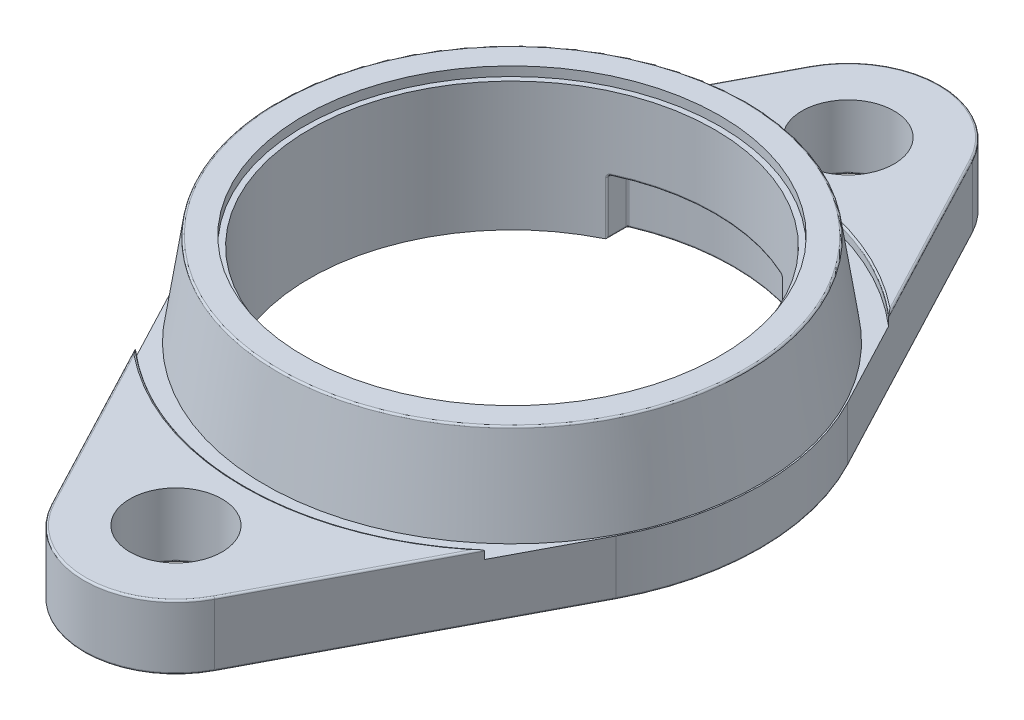
SolidWorks part; units mm, degrees
material "Zinco AC41A Liga, como fundido"
ref_plane "Plano frontal" through (0, 0, 0) normal (0, 0, 1) x (1, 0, 0)
ref_plane "Plano superior" through (0, 0, 0) normal (0, 1, 0) x (1, 0, 0)
ref_plane "Plano direito" through (0, 0, 0) normal (1, 0, 0) x (0, 0, -1)
sketch "Esboço3" plane through (0, 0, 0) normal (0, 1, 0) x (1, 0, 0)
  line L0 (-11.9463, 6.2877) -> (-4.4246, 20.5788)
  line L1 (4.4246, 20.5788) -> (11.9463, 6.2877)
  line L2 (-11.9463, -6.2877) -> (-4.4246, -20.5788)
  line L3 (4.4246, -20.5788) -> (11.9463, -6.2877)
  circle A0 centre (0, 0) radius 11
  arc A1 (-11.9463, 6.2877) -> (-11.9463, -6.2877) centre (0, 0) ccw
  arc A2 (-4.4246, 20.5788) -> (4.4246, 20.5788) centre (0, 18.25) cw
  arc A3 (-4.4246, -20.5788) -> (4.4246, -20.5788) centre (0, -18.25) ccw
  arc A4 (11.9463, -6.2877) -> (11.9463, 6.2877) centre (0, 0) ccw
  circle A5 centre (0, 18.25) radius 2.5
  circle A6 centre (0, -18.25) radius 2.5
  dimension "D1" = 22
  dimension "D2" = 27
  dimension "D4" = 46.5
  dimension "D3" = 5
  dimension "D5" = 5
  dimension "D6" = 5
extrude "Ressalto-extrusão1" add sketch "Esboço3" along normal blind 3
sketch "Esboço4" plane through (0, 0, 0) normal (1, 0, 0) x (0, 0, -1)
  line L0 (0, 0) -> (0, 3) construction
  line L1 (6.2877, 3) -> (-6.2877, 3) construction
  line L2 (-11, 3) -> (-11, 7.5)
  line L3 (-11, 7.5) -> (-11.3, 7.5)
  line L4 (-11.3, 7.5) -> (-11.3, 8)
  line L5 (-11.3, 8) -> (-12.675, 8)
  line L6 (-12.675, 8) -> (-13.425, 3)
  line L7 (-20.5788, 3) -> (-6.2877, 3) construction
  line L8 (-13.425, 3) -> (-11, 3)
  dimension "D1" = 4.5
  dimension "D2" = 12.675
  dimension "D3" = 13.425
  dimension "D4" = 0.5
  dimension "D5" = 0.3
revolve "Revolução1" add sketch "Esboço4" angle 360 about L0
sketch "Esboço6" plane through (0, 3, 0) normal (0, 1, 0) x (1, 0, 0)
  line L0 (-9.4818, 10.9702) -> (-4.4246, 20.5788)
  line L1 (-4.4246, 20.5788) -> (-11.9463, 6.2877) construction
  line L2 (4.4246, 20.5788) -> (9.4818, 10.9702)
  line L3 (11.9463, 6.2877) -> (4.4246, 20.5788) construction
  line L4 (-9.4818, -10.9702) -> (-4.4246, -20.5788)
  line L5 (-11.9463, -6.2877) -> (-4.4246, -20.5788) construction
  line L6 (4.4246, -20.5788) -> (9.4818, -10.9702)
  line L7 (4.4246, -20.5788) -> (11.9463, -6.2877) construction
  arc A0 (-4.4246, 20.5788) -> (4.4246, 20.5788) centre (0, 18.25) cw
  arc A1 (-4.4246, -20.5788) -> (4.4246, -20.5788) centre (0, -18.25) ccw
  arc A2 (-9.4818, -10.9702) -> (9.4818, -10.9702) centre (0, 0) ccw
  arc A3 (9.4818, 10.9702) -> (-9.4818, 10.9702) centre (0, 0) ccw
  dimension "D1" = 29
extrude "Ressalto-extrusão2" add sketch "Esboço6" along normal blind 0.5
sketch "Esboço7" plane through (0, 0, 0) normal (0, -1, 0) x (1, 0, 0)
  line L11 (-2.876, -19.7637) -> (-10.3977, -5.4726)
  line L12 (-10.3977, 5.4726) -> (-2.876, 19.7637)
  line L13 (-4.3256, -17.0094) -> (-10.3977, -5.4726)
  line L14 (-10.3977, 5.4726) -> (-4.3256, 17.0094)
  line L19 (10.3977, -5.4726) -> (2.876, -19.7637)
  line L20 (2.876, 19.7637) -> (10.3977, 5.4726)
  line L21 (10.3977, -5.4726) -> (4.3256, -17.0094)
  line L22 (4.3256, 17.0094) -> (10.3977, 5.4726)
  arc A5 (-10.3977, 5.4726) -> (-10.3977, -5.4726) centre (0, 0) ccw
  arc A6 (-10.3977, 5.4726) -> (-10.3977, -5.4726) centre (0, 0) ccw
  arc A8 (4.3256, -17.0094) -> (-4.3256, -17.0094) centre (0, -18.25) ccw
  arc A9 (10.3977, -5.4726) -> (10.3977, 5.4726) centre (0, 0) ccw
  arc A10 (10.3977, -5.4726) -> (10.3977, 5.4726) centre (0, 0) ccw
  arc A11 (-4.3256, 17.0094) -> (4.3256, 17.0094) centre (0, 18.25) ccw
  dimension "D3" = 9
  dimension "D1" = 1.75
  dimension "D2" = 1.75
extrude "Corte-extrusão1" cut sketch "Esboço7" against normal blind 0.5
sketch "Esboço8" plane through (0, 0.5, 0) normal (0, -1, 0) x (1, 0, 0)
  line L0 (-4.75, 11.0199) -> (-4.75, 9.9216)
  line L1 (4.75, 11.0199) -> (4.75, 9.9216)
  line L2 (0, 0) -> (0, -15.75) construction
  line L3 (-4.75, -9.9216) -> (-4.75, -11.0199)
  line L4 (4.75, -9.9216) -> (4.75, -11.0199)
  arc A0 (-4.75, -11.0199) -> (4.75, -11.0199) centre (0, 0) ccw
  circle A3 centre (0, 0) radius 11 construction
  circle A4 centre (0, -18.25) radius 2.5 construction
  arc A5 (-4.75, -9.9216) -> (4.75, -9.9216) centre (0, 0) ccw
  arc A6 (4.75, 9.9216) -> (-4.75, 9.9216) centre (0, 0) ccw
  arc A7 (4.75, 11.0199) -> (-4.75, 11.0199) centre (0, 0) ccw
  dimension "D1" = 1
  dimension "D2" = 9.5
extrude "Corte-extrusão2" cut sketch "Esboço8" against normal blind 3
fillet "Filete1" radius 0.1 48 edges at (4.75, 0.5, -10.4707) (4.75, 2, -9.9216) (4.75, 0.5, 10.4707) (-4.75, 2, -11.0199) (4.75, 2, -11.0199) (0, 0.5, -12) (-4.75, 3.5, -10.4707) (0, 3.5, -11) (4.75, 3.5, -10.4707) (0, 3.5, -12) (0, 0, 20.75) (-8.1855, 0, 13.4332) (0, 0, 23.25) (8.1855, 0, 13.4332) (13.5, 0, 0) (8.1855, 0, -13.4332) (0, 0, -23.25) (-8.1855, 0, -13.4332) (-13.5, 0, 0) (0, 0, -15.75) (0, 0, 13.75) (-7.3617, 0, 11.241) (-11.75, 0, 0) (-7.3617, 0, -11.241) (0, 0, -13.75) (7.3617, 0, -11.241) (11.75, 0, 0) (7.3617, 0, 11.241) (6.9532, 3.5, 15.7745) (0, 3.5, 23.25) (-6.9532, 3.5, 15.7745) (0, 3.5, 14.5) (-6.9532, 3.5, -15.7745) (0, 3.5, -23.25) (6.9532, 3.5, -15.7745) (0, 3.5, -14.5) (-4.75, 0.5, -10.4707) (-4.75, 2, -9.9216) (4.75, 2, 11.0199) (4.75, 3.5, 10.4707) (0, 0.5, 12) (-4.75, 0.5, 10.4707) (-4.75, 3.5, 10.4707) (0, 3.5, 12) (4.75, 2, 9.9216) (0, 3.5, 11) (-4.75, 2, 9.9216) (0, 8, -12.675)
hole_wizard "Furo de diâmetro Ø5.0 (5)1" positions "3DSketch1" profile "Esboço9" hole size "Ø5.0" standard "ISO"
sketch3d "3DSketch1"
  arc A2 (4.3361, 3.5, -20.5322) -> (-4.3361, 3.5, -20.5322) centre (0, 3.5, -18.25) ccw construction
  arc A3 (-4.3361, 3.5, 20.5322) -> (4.3361, 3.5, 20.5322) centre (0, 3.5, 18.25) ccw construction
  point P0 (0, 3.5, -18.25)
  point P2 (0, 3.5, 18.25)
  point P17 (0, 8.4, -18.25)
  point P23 (0, 8.4, 18.25)
sketch "Esboço9" plane through (0, 3.5, -18.25) normal (1, 0, 0) x (0, 0, 1)
  line L0 (0, 0) -> (0, 12.8522)
  line L1 (0, 12.8522) -> (2.5, 11.35)
  line L2 (2.5, 11.35) -> (2.5, 0)
  line L5 (2.5, 0) -> (0, 0)
  line L10 (0, 12.8522) -> (-2.5, 11.35) construction
  line L11 (0, -6.35) -> (0, 107.95) construction
  dimension "Hole Dia." = 5
  dimension "Hole Depth" = 11.35
  dimension "Drill Angle" = 118
sketch "Sketch2" plane through (0, 0, 0) normal (1, 0, 0) x (0, 0, -1)
  line L0 (-6.2877, 0.1) -> (6.2877, 0.1) construction
  circle A0 centre (0, 3.6) radius 1
  dimension "D1" = 3.5
scale "Scale1" scale about centroid uniform scaling yes scale factor 1.25
scale "Scale2" scale about centroid uniform scaling yes scale factor 1.5
